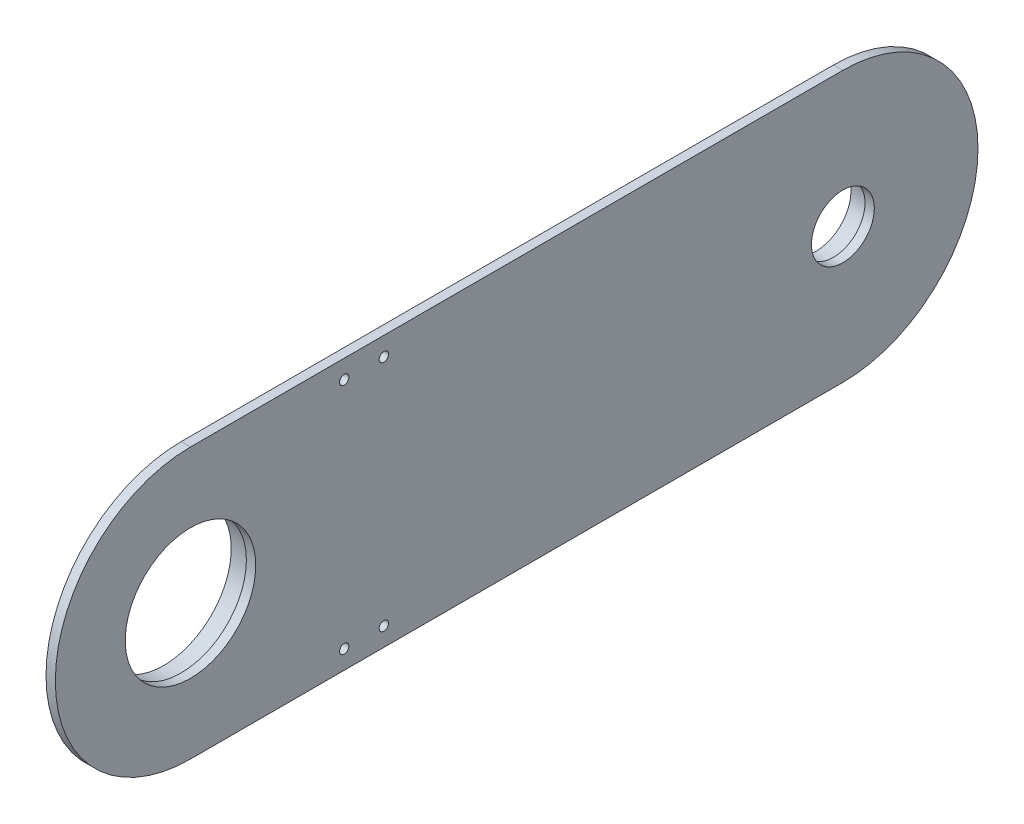
SolidWorks part; units mm, degrees
ref_plane "Front Plane" through (0, 0, 0) normal (0, 0, 1) x (1, 0, 0)
ref_plane "Top Plane" through (0, 0, 0) normal (0, 1, 0) x (1, 0, 0)
ref_plane "Right Plane" through (0, 0, 0) normal (1, 0, 0) x (0, 0, -1)
sketch "Sketch1" plane through (0, 0, 0) normal (1, 0, 0) x (0, 0, -1)
  line L0 (0, 0) -> (280, 0) construction
  line L1 (0, 58) -> (280, 58)
  line L2 (0, -58) -> (280, -58)
  arc A0 (0, 58) -> (0, -58) centre (0, 0) ccw
  arc A1 (280, -58) -> (280, 58) centre (280, 0) ccw
  circle A2 centre (0, 0) radius 28
  circle A3 centre (280, 0) radius 13.5
  point P3 (140, 0)
  dimension "D2" = 58
  dimension "D3" = 56
  dimension "D4" = 27
  dimension "D1" = 280
extrude "Boss-Extrude1" add sketch "Sketch1" along normal blind 4
ref_plane "Plane1" through (-7.5, 0, 0) normal (-1, 0, 0) x (0, 0, 1)
sketch "Sketch2" plane through (-7.5, 0, 0) normal (-1, 0, 0) x (0, 0, 1)
  line L0 (-140, 58) -> (-140, -58) construction
  line L1 (-280, 58) -> (0, 58) construction
  line L2 (0, -58) -> (-280, -58) construction
  circle A0 centre (0, 0) radius 29
  circle A1 centre (0, 0) radius 34
  circle A2 centre (-280, 0) radius 15
  circle A3 centre (-280, 0) radius 20
  dimension "D1" = 58
  dimension "D2" = 68
  dimension "D3" = 30
  dimension "D4" = 40
extrude "Boss-Extrude2" add sketch "Sketch2" against normal up to surface (7.5 mm away) up to face at (0, 0, -140)
chamfer "Chamfer1" distance 8 angle 45 2 edges at (0, 0, -34) (0, 0, -300)
sketch "Sketch3" plane through (0, 0, 0) normal (-1, 0, 0) x (0, 0, 1)
  line L0 (0, 58) -> (-73, 58) construction
  line L1 (-280, 58) -> (0, 58) construction
  line L2 (-73, 58) -> (-73, -58) construction
  line L3 (0, -58) -> (-280, -58) construction
  line L4 (-73, 58) -> (-76, 58) construction
  line L5 (-76, 58) -> (-76, -58) construction
  line L6 (-69.0931, 53.5) -> (-66, 53.5) construction
  line L7 (-66, 46.5) -> (-69.0931, 46.5) construction
  line L8 (-66, 50) -> (-73, 50) construction
  line L9 (-73, 55.8533) -> (-73, 44.1467) construction
  line L10 (-73, 0) -> (-99.886, 0) construction
  line L11 (-74.5, 58) -> (-74.5, 37.4458) construction
  arc A0 (-69.0931, 53.5) -> (-73, 55.8533) centre (-69.0931, 57.9197) cw construction
  arc A1 (-66, 53.5) -> (-66, 46.5) centre (-66, 50) cw construction
  arc A2 (-69.0931, 46.5) -> (-73, 44.1467) centre (-69.0931, 42.0803) ccw construction
  circle A3 centre (-66, 50) radius 2
  circle A4 centre (-66, -50) radius 2
  circle A5 centre (-83, -50) radius 2
  circle A6 centre (-83, 50) radius 2
  dimension "D3" = 4
  dimension "D1" = 73
  dimension "D2" = 3
  dimension "D4" = 7
  dimension "D5" = 8
  dimension "D6" = 7
extrude "Cut-Extrude1" cut sketch "Sketch3" against normal through all contours A3 | A4 | A6 | A5
equation "\"mini-flipper-shaft-diameter\"= 26mm"
equation "\"mini-shaft-ring-groove-diam\"= 7.8mm"
equation "\"mini-shaft-ring-groove-width\"= 1mm"
equation "\"dtCoverPlate-DistFrom-GearCent\" = 73mm"
equation "\"wormGearShaft-L\" = \"dtCoverPlate-DistFrom-GearCent\" - 27.75 + 3.75"
equation "\"D1@Sketch3\"=\"dtCoverPlate-DistFrom-GearCent\""
